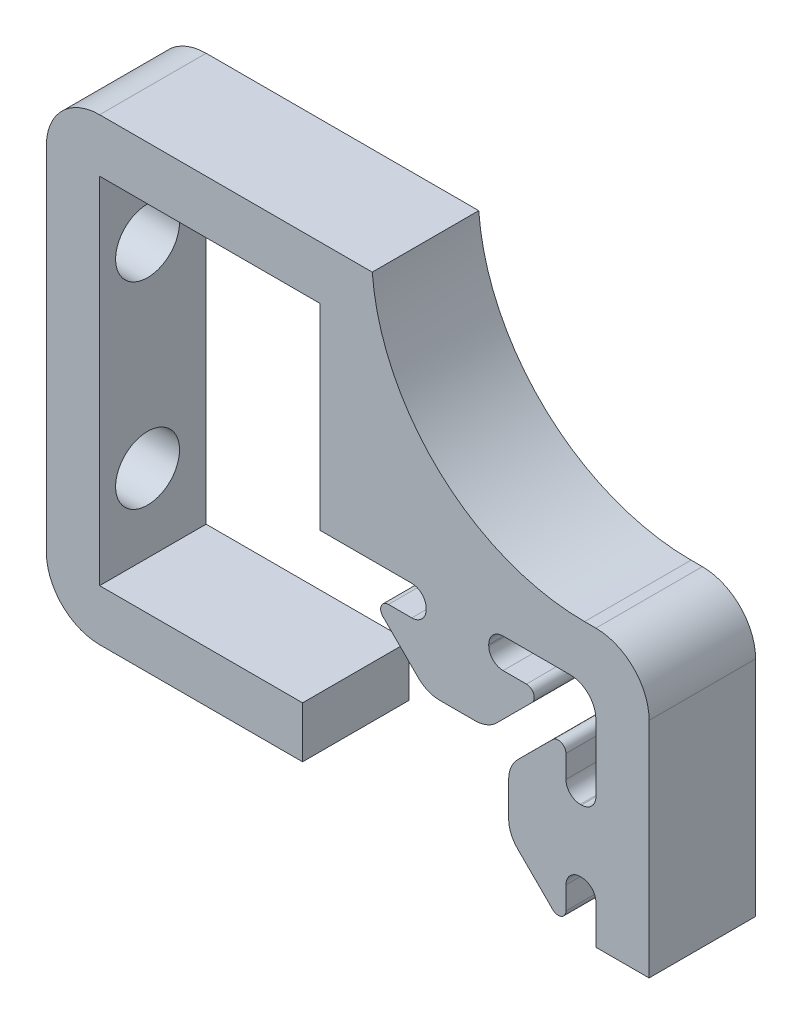
SolidWorks part; units mm, degrees
ref_plane "Front Plane" through (0, 0, 0) normal (0, 0, 1) x (1, 0, 0)
ref_plane "Top Plane" through (0, 0, 0) normal (0, 1, 0) x (1, 0, 0)
ref_plane "Right Plane" through (0, 0, 0) normal (1, 0, 0) x (0, 0, -1)
sketch "Sketch1" plane through (0, 0, 0) normal (0, 0, 1) x (1, 0, 0)
  line L1 (-4.3059, -13) -> (-4.2875, -13)
  line L11 (13, -7.9544) -> (13, -5.3171)
  line L12 (13, -5.3171) -> (13, -4.2875)
  line L13 (11.651, -2.9385) -> (11.5392, -2.9385)
  line L14 (10.1902, -4.2875) -> (10.1902, -6.4021)
  line L15 (8.949, -6.917) -> (5.6529, -3.6284)
  line L16 (4.8085, -1.5932) -> (4.8085, 1.5932)
  line L17 (5.6529, 3.6284) -> (8.949, 6.917)
  line L18 (10.1902, 6.4021) -> (10.1902, 4.2875)
  line L19 (11.5392, 2.9385) -> (11.651, 2.9385)
  line L20 (13, 4.2875) -> (13, 5.3171)
  line L21 (13, 7.9544) -> (13, 10.5918)
  line L22 (10.5918, 13) -> (5.3216, 13)
  line L23 (5.3216, 13) -> (4.2875, 13)
  line L24 (2.9385, 11.651) -> (2.9385, 11.5392)
  line L25 (4.2875, 10.1902) -> (6.4768, 10.1902)
  line L26 (6.9951, 8.9367) -> (3.6864, 5.6355)
  line L27 (1.6558, 4.7958) -> (-1.6558, 4.7958)
  line L28 (-3.6864, 5.6355) -> (-6.9951, 8.9367)
  line L29 (-6.4768, 10.1902) -> (-4.2875, 10.1902)
  line L30 (-2.9385, 11.5392) -> (-2.9385, 11.651)
  line L31 (-4.2875, 13) -> (-4.3059, 13)
  line L32 (-4.3059, 13) -> (-12.9, 13)
  line L33 (-13, 10.5918) -> (-13, 5.3171) construction
  line L34 (-13, 5.3171) -> (-13, 4.2875) construction
  line L35 (-11.651, 2.9385) -> (-11.5392, 2.9385) construction
  line L36 (-10.1902, 4.2875) -> (-10.1902, 6.4021) construction
  line L37 (-8.949, 6.917) -> (-5.6529, 3.6284) construction
  line L38 (-4.8085, 1.5932) -> (-4.8085, -1.5932) construction
  line L39 (-5.6529, -3.6284) -> (-8.949, -6.917) construction
  line L40 (-10.1902, -6.4021) -> (-10.1902, -4.2875) construction
  line L41 (-11.5392, -2.9385) -> (-11.651, -2.9385) construction
  line L43 (18, -7.9544) -> (18, 18)
  line L44 (13, 5.3171) -> (13, 7.9544)
  line L45 (-33.4, 31.3527) -> (-13, 31.3527) construction
  line L46 (-33.4, 31.3527) -> (-33.4, -1.6473) construction
  line L47 (-33.4, -1.6473) -> (-13, -1.6473) construction
  line L48 (-13, 31.3527) -> (-13, -1.6473) construction
  line L53 (-18, -6.6473) -> (-38.6, -6.6473)
  line L54 (-38.6, -6.6473) -> (-38.6, 36.4527)
  line L55 (-38.6, 36.4527) -> (-8, 36.4527)
  line L57 (-12.9, 31.4527) -> (-33.6, 31.4527)
  line L58 (-33.6, 31.4527) -> (-33.6, -1.8473)
  line L59 (-33.6, -1.8473) -> (-14.5421, -1.8473)
  line L61 (18, 18) -> (-8, 18)
  line L62 (-8, 18) -> (-8, 36.4527)
  line L63 (13, -7.9544) -> (18, -7.9544)
  line L64 (-12.9, 31.4527) -> (-12.9, 13)
  line L65 (-4.3059, 13) -> (-10.5918, 13) construction
  line L66 (-18, -6.6473) -> (-14.5421, -6.6473)
  line L67 (-14.5421, -6.6473) -> (-14.5421, -1.8473)
  line L68 (13, -10.5918) -> (13, -5.3171) construction
  line L88 (-7.1797, -8.6452) -> (-3.9523, -5.4237) construction
  line L89 (-1.7093, -4.4958) -> (1.7093, -4.4958) construction
  line L90 (3.9523, -5.4237) -> (7.1797, -8.6452) construction
  line L91 (6.4164, -10.4902) -> (4.2875, -10.4902) construction
  line L92 (3.2385, -11.5392) -> (3.2385, -11.651) construction
  line L93 (4.2875, -12.7) -> (5.3216, -12.7) construction
  line L94 (5.3216, -12.7) -> (10.5918, -12.7) construction
  line L95 (12.7, -10.5918) -> (12.7, -5.3171) construction
  line L96 (12.7, -5.3171) -> (12.7, -4.2875) construction
  line L97 (11.651, -3.2385) -> (11.5392, -3.2385) construction
  line L98 (10.4902, -4.2875) -> (10.4902, -6.4021) construction
  line L99 (8.7371, -7.1294) -> (5.441, -3.8408) construction
  line L100 (4.5085, -1.5932) -> (4.5085, 1.5932) construction
  line L101 (5.441, 3.8408) -> (8.7371, 7.1294) construction
  line L102 (10.4902, 6.4021) -> (10.4902, 4.2875) construction
  line L103 (11.5392, 3.2385) -> (11.651, 3.2385) construction
  line L104 (12.7, 4.2875) -> (12.7, 5.3171) construction
  line L105 (12.7, 5.3171) -> (12.7, 10.5918) construction
  line L106 (10.5918, 12.7) -> (5.3216, 12.7) construction
  line L107 (5.3216, 12.7) -> (4.2875, 12.7) construction
  line L108 (3.2385, 11.651) -> (3.2385, 11.5392) construction
  line L109 (4.2875, 10.4902) -> (6.4768, 10.4902) construction
  line L110 (7.207, 8.7244) -> (3.8983, 5.4232) construction
  line L111 (1.6558, 4.4958) -> (-1.6558, 4.4958) construction
  line L112 (-3.8983, 5.4232) -> (-7.207, 8.7244) construction
  line L113 (-6.4768, 10.4902) -> (-4.2875, 10.4902) construction
  line L114 (-3.2385, 11.5392) -> (-3.2385, 11.651) construction
  line L115 (-4.2875, 12.7) -> (-4.3059, 12.7) construction
  line L116 (-4.3059, 12.7) -> (-10.5918, 12.7) construction
  line L117 (-12.7, 10.5918) -> (-12.7, 5.3171) construction
  line L118 (-12.7, 5.3171) -> (-12.7, 4.2875) construction
  line L119 (-11.651, 3.2385) -> (-11.5392, 3.2385) construction
  line L120 (-10.4902, 4.2875) -> (-10.4902, 6.4021) construction
  line L121 (-8.7371, 7.1294) -> (-5.441, 3.8408) construction
  line L122 (-4.5085, 1.5932) -> (-4.5085, -1.5932) construction
  line L123 (-5.441, -3.8408) -> (-8.7371, -7.1294) construction
  line L124 (-10.4902, -6.4021) -> (-10.4902, -4.2875) construction
  line L125 (-11.5392, -3.2385) -> (-11.651, -3.2385) construction
  line L126 (-12.7, -4.2875) -> (-12.7, -5.3171) construction
  line L127 (-12.7, -5.3171) -> (-12.7, -10.5918) construction
  line L128 (-10.5918, -12.7) -> (-4.3059, -12.7) construction
  line L129 (-4.3059, -12.7) -> (-4.2875, -12.7) construction
  line L130 (-3.2385, -11.651) -> (-3.2385, -11.5392) construction
  line L131 (-4.2875, -10.4902) -> (-6.4164, -10.4902) construction
  line L132 (-13, -4.2875) -> (-13, -5.3171) construction
  line L133 (-13, -5.3171) -> (-13, -10.5918) construction
  line L134 (-10.5918, -13) -> (-4.3059, -13) construction
  line L135 (-4.2875, -10.1902) -> (-6.4164, -10.1902) construction
  line L136 (-6.9677, -8.8575) -> (-3.7403, -5.636) construction
  line L137 (-1.7093, -4.7958) -> (1.7093, -4.7958) construction
  line L138 (3.7403, -5.636) -> (6.9677, -8.8575) construction
  line L139 (6.4164, -10.1902) -> (4.2875, -10.1902) construction
  line L140 (2.9385, -11.5392) -> (2.9385, -11.651) construction
  line L141 (4.2875, -13) -> (5.3216, -13) construction
  line L142 (5.3216, -13) -> (10.5918, -13) construction
  line L143 (-2.9385, -11.651) -> (-2.9385, -11.5392) construction
  line L144 (13, 5.3171) -> (13, 10.5918) construction
  arc A4 (-1.7093, -4.7958) -> (-3.7403, -5.636) centre (-1.7093, -7.6708) ccw
  arc A9 (13, -4.2875) -> (11.651, -2.9385) centre (11.651, -4.2875) ccw
  arc A10 (11.5392, -2.9385) -> (10.1902, -4.2875) centre (11.5392, -4.2875) ccw
  arc A11 (8.949, -6.917) -> (10.1902, -6.4021) centre (9.4628, -6.4021) ccw
  arc A12 (4.8085, -1.5932) -> (5.6529, -3.6284) centre (7.6835, -1.5932) ccw
  arc A13 (5.6529, 3.6284) -> (4.8085, 1.5932) centre (7.6835, 1.5932) ccw
  arc A14 (10.1902, 6.4021) -> (8.949, 6.917) centre (9.4628, 6.4021) ccw
  arc A15 (10.1902, 4.2875) -> (11.5392, 2.9385) centre (11.5392, 4.2875) ccw
  arc A16 (11.651, 2.9385) -> (13, 4.2875) centre (11.651, 4.2875) ccw
  arc A17 (4.2875, 13) -> (2.9385, 11.651) centre (4.2875, 11.651) ccw
  arc A18 (2.9385, 11.5392) -> (4.2875, 10.1902) centre (4.2875, 11.5392) ccw
  arc A19 (6.9951, 8.9367) -> (6.4768, 10.1902) centre (6.4768, 9.4563) ccw
  arc A20 (1.6558, 4.7958) -> (3.6864, 5.6355) centre (1.6558, 7.6708) ccw
  arc A21 (-3.6864, 5.6355) -> (-1.6558, 4.7958) centre (-1.6558, 7.6708) ccw
  arc A22 (-6.4768, 10.1902) -> (-6.9951, 8.9367) centre (-6.4768, 9.4563) ccw
  arc A23 (-4.2875, 10.1902) -> (-2.9385, 11.5392) centre (-4.2875, 11.5392) ccw
  arc A24 (-2.9385, 11.651) -> (-4.2875, 13) centre (-4.2875, 11.651) ccw
  arc A25 (-13, 4.2875) -> (-11.651, 2.9385) centre (-11.651, 4.2875) ccw construction
  arc A26 (-11.5392, 2.9385) -> (-10.1902, 4.2875) centre (-11.5392, 4.2875) ccw construction
  arc A27 (-8.949, 6.917) -> (-10.1902, 6.4021) centre (-9.4628, 6.4021) ccw construction
  arc A28 (-4.8085, 1.5932) -> (-5.6529, 3.6284) centre (-7.6835, 1.5932) ccw construction
  arc A29 (-5.6529, -3.6284) -> (-4.8085, -1.5932) centre (-7.6835, -1.5932) ccw construction
  arc A30 (-10.1902, -6.4021) -> (-8.949, -6.917) centre (-9.4628, -6.4021) ccw construction
  arc A31 (-10.1902, -4.2875) -> (-11.5392, -2.9385) centre (-11.5392, -4.2875) ccw construction
  arc A32 (-11.651, -2.9385) -> (-13, -4.2875) centre (-11.651, -4.2875) ccw construction
  arc A34 (13, 10.5918) -> (10.5628, 12.9998) centre (10.5918, 10.5918) ccw
  arc A35 (-10.5628, 12.9998) -> (-12.9998, 10.5628) centre (-10.5918, 10.5918) ccw construction
  arc A37 (12.9998, 10.5628) -> (10.5628, 12.9998) centre (10.5918, 10.5918) ccw construction
  arc A104 (-7.1797, -8.6452) -> (-6.4164, -10.4902) centre (-6.4164, -9.4098) ccw construction
  arc A105 (-1.7093, -4.4958) -> (-3.9523, -5.4237) centre (-1.7093, -7.6708) ccw construction
  arc A106 (3.9523, -5.4237) -> (1.7093, -4.4958) centre (1.7093, -7.6708) ccw construction
  arc A107 (6.4164, -10.4902) -> (7.1797, -8.6452) centre (6.4164, -9.4098) ccw construction
  arc A108 (4.2875, -10.4902) -> (3.2385, -11.5392) centre (4.2875, -11.5392) ccw construction
  arc A109 (3.2385, -11.651) -> (4.2875, -12.7) centre (4.2875, -11.651) ccw construction
  arc A112 (10.5664, -12.6998) -> (12.6998, -10.5664) centre (10.5918, -10.5918) ccw construction
  arc A115 (12.7, -4.2875) -> (11.651, -3.2385) centre (11.651, -4.2875) ccw construction
  arc A116 (11.5392, -3.2385) -> (10.4902, -4.2875) centre (11.5392, -4.2875) ccw construction
  arc A117 (8.7371, -7.1294) -> (10.4902, -6.4021) centre (9.4628, -6.4021) ccw construction
  arc A118 (4.5085, -1.5932) -> (5.441, -3.8408) centre (7.6835, -1.5932) ccw construction
  arc A119 (5.441, 3.8408) -> (4.5085, 1.5932) centre (7.6835, 1.5932) ccw construction
  arc A120 (10.4902, 6.4021) -> (8.7371, 7.1294) centre (9.4628, 6.4021) ccw construction
  arc A121 (10.4902, 4.2875) -> (11.5392, 3.2385) centre (11.5392, 4.2875) ccw construction
  arc A122 (11.651, 3.2385) -> (12.7, 4.2875) centre (11.651, 4.2875) ccw construction
  arc A125 (12.6998, 10.5664) -> (10.5664, 12.6998) centre (10.5918, 10.5918) ccw construction
  arc A128 (4.2875, 12.7) -> (3.2385, 11.651) centre (4.2875, 11.651) ccw construction
  arc A129 (3.2385, 11.5392) -> (4.2875, 10.4902) centre (4.2875, 11.5392) ccw construction
  arc A130 (7.207, 8.7244) -> (6.4768, 10.4902) centre (6.4768, 9.4563) ccw construction
  arc A131 (1.6558, 4.4958) -> (3.8983, 5.4232) centre (1.6558, 7.6708) ccw construction
  arc A132 (-3.8983, 5.4232) -> (-1.6558, 4.4958) centre (-1.6558, 7.6708) ccw construction
  arc A133 (-6.4768, 10.4902) -> (-7.207, 8.7244) centre (-6.4768, 9.4563) ccw construction
  arc A134 (-4.2875, 10.4902) -> (-3.2385, 11.5392) centre (-4.2875, 11.5392) ccw construction
  arc A135 (-3.2385, 11.651) -> (-4.2875, 12.7) centre (-4.2875, 11.651) ccw construction
  arc A138 (-10.5664, 12.6998) -> (-12.6998, 10.5664) centre (-10.5918, 10.5918) ccw construction
  arc A141 (-12.7, 4.2875) -> (-11.651, 3.2385) centre (-11.651, 4.2875) ccw construction
  arc A142 (-11.5392, 3.2385) -> (-10.4902, 4.2875) centre (-11.5392, 4.2875) ccw construction
  arc A143 (-8.7371, 7.1294) -> (-10.4902, 6.4021) centre (-9.4628, 6.4021) ccw construction
  arc A144 (-4.5085, 1.5932) -> (-5.441, 3.8408) centre (-7.6835, 1.5932) ccw construction
  arc A145 (-5.441, -3.8408) -> (-4.5085, -1.5932) centre (-7.6835, -1.5932) ccw construction
  arc A146 (-10.4902, -6.4021) -> (-8.7371, -7.1294) centre (-9.4628, -6.4021) ccw construction
  arc A147 (-10.4902, -4.2875) -> (-11.5392, -3.2385) centre (-11.5392, -4.2875) ccw construction
  arc A148 (-11.651, -3.2385) -> (-12.7, -4.2875) centre (-11.651, -4.2875) ccw construction
  arc A151 (-12.6998, -10.5664) -> (-10.5918, -12.7) centre (-10.5918, -10.5918) ccw construction
  arc A154 (-4.2875, -12.7) -> (-3.2385, -11.651) centre (-4.2875, -11.651) ccw construction
  arc A155 (-3.2385, -11.5392) -> (-4.2875, -10.4902) centre (-4.2875, -11.5392) ccw construction
  arc A156 (-4.2875, -13) -> (-2.9385, -11.651) centre (-4.2875, -11.651) ccw construction
  arc A157 (-2.9385, -11.5392) -> (-4.2875, -10.1902) centre (-4.2875, -11.5392) ccw construction
  arc A158 (-6.9677, -8.8575) -> (-6.4164, -10.1902) centre (-6.4164, -9.4098) ccw construction
  arc A159 (3.7403, -5.636) -> (1.7093, -4.7958) centre (1.7093, -7.6708) ccw construction
  arc A160 (6.4164, -10.1902) -> (6.9677, -8.8575) centre (6.4164, -9.4098) ccw construction
  arc A161 (4.2875, -10.1902) -> (2.9385, -11.5392) centre (4.2875, -11.5392) ccw construction
  arc A162 (2.9385, -11.651) -> (4.2875, -13) centre (4.2875, -11.651) ccw construction
  dimension "D2" = 33
  dimension "D3" = 20.4
  dimension "D4" = 5
  dimension "D5" = 5
  dimension "D6" = 5
  dimension "D7" = 0.2
  dimension "D9" = 5
  dimension "D10" = 5
  dimension "D11" = 5
  dimension "D12" = 0.2
  dimension "D13" = 0.2
  dimension ".2" = 0.2
  dimension "D1" = 0.3
extrude "Boss-Extrude1" add sketch "Sketch1" along normal blind 10 contours L59 L58 L57 L55 L54 L53 L44 L20 A16 L19 A15 L18 A14 L17 A13 L16 A12 L15 A11 L14 A10 L13 A9 L12 L11 A4 region at (-11.6511, 13.3006, 0)
sketch "Sketch2" plane through (-38.6, 0, 0) normal (-1, 0, 0) x (0, 0, 1)
  line L0 (0, -6.6473) -> (0, 36.4527) construction
  line L3 (4.5, 26.9527) -> (4.5, 23.9527) construction
  line L4 (10, 31.4527) -> (0, 31.4527) construction
  line L5 (4.5, 8.4527) -> (4.5, 2.4527) construction
  line L6 (4.5, 23.9527) -> (4.5, 20.9527) construction
  circle A0 centre (4.5, 23.9527) radius 3
  circle A1 centre (4.5, 5.4527) radius 3
  dimension "D1" = 6
  dimension "D3" = 6
  dimension "D2" = 7.5
  dimension "D4" = 12.5
  dimension "D5" = 4.5
extrude "Cut-Extrude1" cut sketch "Sketch2" against normal up to next
fillet "Fillet1" radius 20 1 edges at (-8, 18, 5)
fillet "Fillet2" radius 5 3 edges at (-38.6, -6.6473, 5) (18, 18, 5) (-38.6, 36.4527, 5)
mirror "Mirror1" about plane through (0, 0, 0) normal (0, 0, 1) of bodies 102
sketch "Sketch3" plane through (-38.6, 0, 0) normal (-1, 0, 0) x (0, 0, 1)
  line L1 (0, 49.9999) -> (29.852, 49.9999)
  line L2 (29.852, 49.9999) -> (29.852, -34.6676)
  line L3 (29.852, -34.6676) -> (0, -34.6676)
  line L5 (0, 49.9999) -> (0, -34.6676)
extrude "Cut-Extrude2" cut sketch "Sketch3" against normal blind 125
